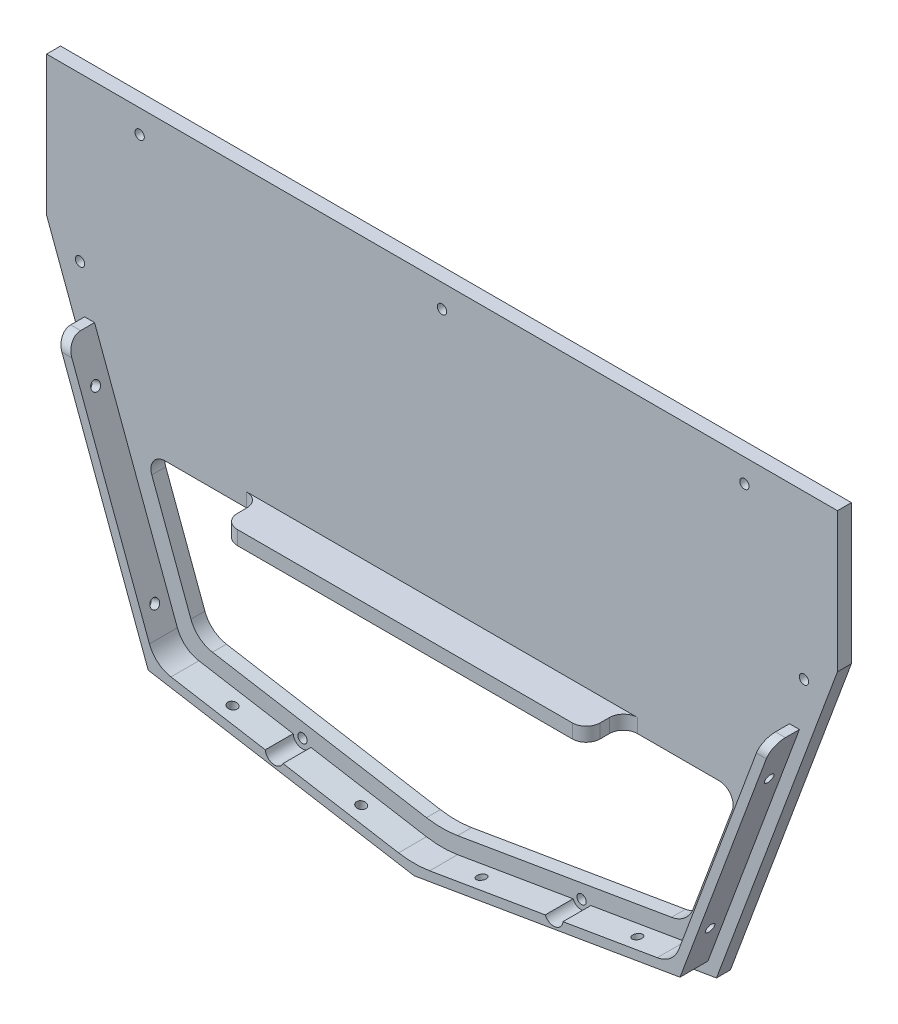
SolidWorks part; units mm, degrees
material "ABS"
ref_plane "Front Plane" through (0, 0, 0) normal (0, 0, 1) x (1, 0, 0)
ref_plane "Top Plane" through (0, 0, 0) normal (0, 1, 0) x (1, 0, 0)
ref_plane "Right Plane" through (0, 0, 0) normal (1, 0, 0) x (0, 0, -1)
sketch "Sketch2" plane through (0, 0, 0) normal (0, 0, 1) x (1, 0, 0)
  line L1 (63.8855, -33) -> (52.7622, -62.9425)
  line L2 (52.7622, -62.9425) -> (0, -71.8859)
  line L3 (-63.8855, -33) -> (63.8855, -33)
  line L4 (0, -71.8859) -> (-52.7622, -62.9425)
  line L5 (-52.7622, -62.9425) -> (-63.8855, -33)
  line L14 (85, 0) -> (85, 30)
  line L15 (85, 30) -> (-85, 30)
  line L16 (-85, 30) -> (-85, 0)
  line L17 (-85, 0) -> (-58.9956, -70)
  line L18 (-58.9956, -70) -> (0, -80)
  line L19 (0, -80) -> (58.9956, -70)
  line L20 (58.9956, -70) -> (85, 0)
extrude "Boss-Extrude1" add sketch "Sketch2" along normal blind 3
sketch "Sketch3" plane through (0, 0, 3) normal (0, 0, 1) x (1, 0, 0)
  line L0 (-74.6918, -14.8259) -> (-55.6821, -65.9975)
  line L3 (-55.6821, -65.9975) -> (0, -75.4358)
  line L20 (-76.8254, -14.8259) -> (-57.1548, -67.7764)
  line L21 (-57.1548, -67.7764) -> (0, -77.4643)
  line L22 (0, -77.4643) -> (57.1548, -67.7764)
  line L23 (57.1548, -67.7764) -> (76.8254, -14.8259)
  line L25 (0, -75.4358) -> (55.6821, -65.9975)
  line L26 (55.6821, -65.9975) -> (74.6918, -14.8259)
  line L27 (-76.8254, -14.8259) -> (-74.6918, -14.8259)
  line L28 (74.6918, -14.8259) -> (76.8254, -14.8259)
  line L29 (55.6821, -65.9975) -> (74.9506, -14.1294) construction
  line L30 (-74.9506, -14.1294) -> (-55.6821, -65.9975) construction
  dimension "D1" = 2
extrude "Boss-Extrude2" add sketch "Sketch3" along normal blind 6
fillet "Fillet1" radius 20 2 edges at (0, -75.4358, 6) (0, -71.8859, 1.5)
fillet "Fillet2" radius 6 4 edges at (-52.7622, -62.9425, 1.5) (-55.6821, -65.9975, 6) (55.6821, -65.9975, 6) (52.7622, -62.9425, 1.5)
fillet "Fillet4" radius 3 2 edges at (-63.8855, -33, 1.5) (63.8855, -33, 1.5)
sketch "Sketch4" plane through (0, 0, 3) normal (0, 0, 1) x (1, 0, 0)
  line L0 (59.5707, -33) -> (-59.5707, -33) construction
  line L1 (-38.9956, -33) -> (38.9956, -33)
  line L2 (-38.9956, -33) -> (-38.9956, -30)
  line L3 (-38.9956, -30) -> (38.9956, -30)
  line L4 (38.9956, -33) -> (38.9956, -30)
  dimension "D1" = 3
  dimension "D2" = 20
  dimension "D3" = 20
extrude "Boss-Extrude3" add sketch "Sketch4" along normal blind 8
fillet "Fillet5" radius 3 4 edges at (38.9956, -31.5, 3) (-38.9956, -31.5, 3) (-38.9956, -31.5, 11) (38.9956, -31.5, 11)
sketch "Sketch5" plane through (0, 0, 3) normal (0, 0, 1) x (1, 0, 0)
  line L0 (85, 30) -> (-85, 30) construction
  line L1 (0, 30) -> (0, 22.9008) construction
  line L2 (85, 0) -> (85, 30) construction
  line L3 (-85, 0) -> (85, 0) construction
  line L4 (-85, 0) -> (-58.9956, -70) construction
  line L5 (58.9956, -70) -> (85, 0) construction
  line L6 (-3.3424, -74.8693) -> (-52.2667, -66.5764) construction
  line L7 (52.2667, -66.5764) -> (3.3424, -74.8693) construction
  circle A0 centre (-65, 25) radius 1
  circle A1 centre (65, 25) radius 1
  circle A2 centre (0, 25) radius 1
  circle A3 centre (-77.8087, -5) radius 1
  circle A4 centre (77.8087, -5) radius 1
  circle A5 centre (-30, -69.8436) radius 1
  circle A6 centre (30, -69.8436) radius 1
  dimension "D1" = 5
  dimension "D2" = 5
  dimension "D3" = 5
  dimension "D5" = 20
  dimension "D6" = 5
  dimension "D7" = 5
  dimension "D8" = 5
  dimension "D10" = 0.5
  dimension "D11" = 0.5
  dimension "D12" = 30
  dimension "D13" = 30
  dimension "D4" = 20
  dimension "D9" = 5
extrude "Cut-Extrude1" cut sketch "Sketch5" against normal blind 3 and the other way through all
sketch "Sketch6" plane through (0, 0, 9) normal (0, 0, 1) x (1, 0, 0)
  circle A0 centre (30, -69.8436) radius 2
  circle A1 centre (-30, -69.8436) radius 2
extrude "Cut-Extrude2" cut sketch "Sketch6" against normal up to surface (6 mm away) up to face at (0, -56.5071, 3)
fillet "Fillet6" radius 3 2 edges at (-75.7586, -14.8259, 9) (75.7586, -14.8259, 9)
sketch "Sketch7" plane through (-72.3486, -26.8768, 0) normal (-0.9374, -0.3482, 0) x (0, 0, 1)
  line L0 (6, -43.6305) -> (6, 12.8556) construction
  line L1 (9, -43.6305) -> (3, -43.6305) construction
  line L2 (6, 12.8556) -> (3, 12.8556) construction
  circle A0 centre (6, 2.8556) radius 1
  circle A1 centre (6, -33.6305) radius 1
  dimension "D1" = 10
  dimension "D2" = 10
extrude "Cut-Extrude3" cut sketch "Sketch7" against normal blind 3
sketch "Sketch8" plane through (72.3486, -26.8768, 0) normal (0.9374, -0.3482, 0) x (0, 0, -1)
  line L0 (-6, -43.6305) -> (-6, 12.8556) construction
  line L1 (-9, -43.6305) -> (-3, -43.6305) construction
  line L2 (-6, 12.8556) -> (-3, 12.8556) construction
  circle A0 centre (-6, 2.8556) radius 1
  circle A1 centre (-6, -33.6305) radius 1
  dimension "D1" = 10
  dimension "D2" = 10
extrude "Cut-Extrude4" cut sketch "Sketch8" against normal blind 3
sketch "Sketch9" plane through (-12.4296, -73.329, 0) normal (0.1671, 0.9859, 0) x (0.9859, -0.1671, 0)
  line L0 (12.9459, -6) -> (-45.0242, -6) construction
  line L1 (12.9459, -9) -> (12.9459, -3) construction
  line L2 (-45.0242, -9) -> (-45.0242, -3) construction
  line L3 (13.0306, -3) -> (13.0306, -139.9824) construction
  circle A0 centre (-1.9694, -6) radius 1
  circle A1 centre (-30.0242, -6) radius 1
  dimension "D1" = 15
  dimension "D2" = 15
extrude "Cut-Extrude5" cut sketch "Sketch9" against normal blind 3
sketch "Sketch10" plane through (12.7638, -75.3008, 0) normal (0.1671, -0.9859, 0) x (0.9859, 0.1671, 0)
  line L0 (45.0242, 6) -> (-12.9459, 6) construction
  line L1 (45.0242, 9) -> (45.0242, 3) construction
  line L2 (-12.9459, 9) -> (-12.9459, 3) construction
  circle A0 centre (-0.9459, 6) radius 1
  circle A1 centre (33.0242, 6) radius 1
  dimension "D1" = 12
  dimension "D2" = 12
extrude "Cut-Extrude6" cut sketch "Sketch10" against normal blind 3
